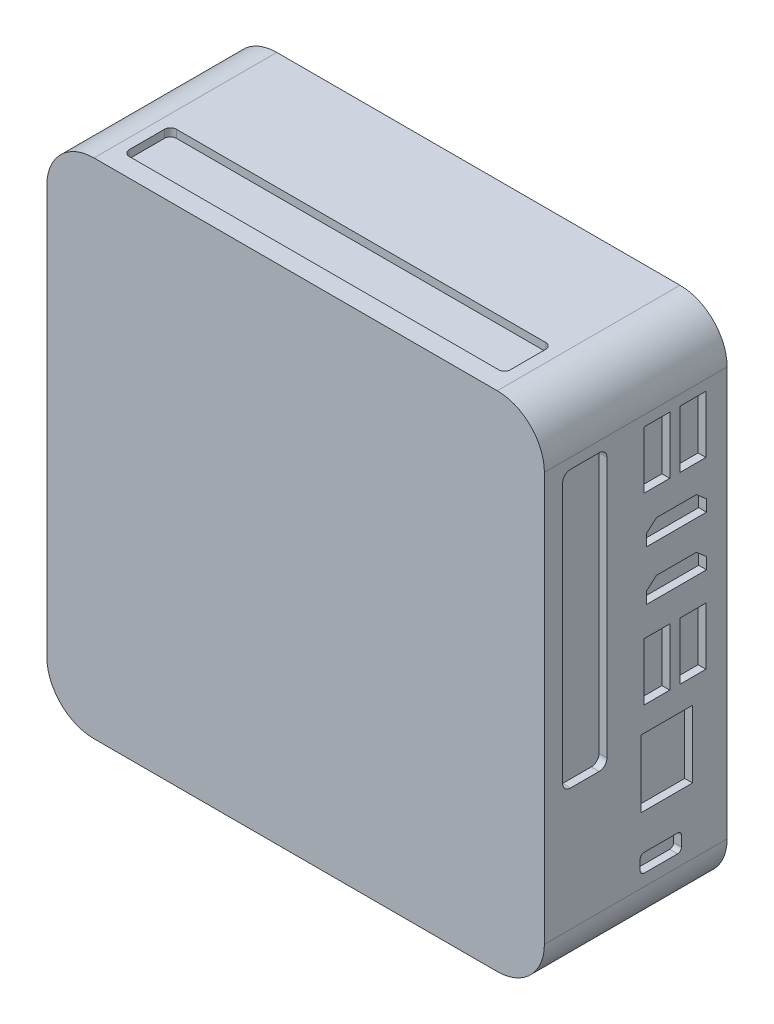
SolidWorks part; units mm, degrees
ref_plane "Płaszczyzna przednia" through (0, 0, 0) normal (0, 0, 1) x (1, 0, 0)
ref_plane "Płaszczyzna górna" through (0, 0, 0) normal (0, 1, 0) x (1, 0, 0)
ref_plane "Płaszczyzna prawa" through (0, 0, 0) normal (1, 0, 0) x (0, 0, -1)
sketch "Szkic1" plane through (0, 0, 0) normal (0, 0, 1) x (1, 0, 0)
  line L1 (-51.3, -64) -> (51.3, -64)
  line L2 (-63.3, -52) -> (-63.3, 52)
  line L3 (-51.3, 64) -> (51.3, 64)
  line L4 (63.3, -52) -> (63.3, 52)
  line L5 (-63.3, -64) -> (63.3, 64) construction
  line L6 (-63.3, 64) -> (63.3, -64) construction
  arc A0 (-51.3, -64) -> (-63.3, -52) centre (-51.3, -52) cw
  arc A1 (51.3, -64) -> (63.3, -52) centre (51.3, -52) ccw
  arc A2 (51.3, 64) -> (63.3, 52) centre (51.3, 52) cw
  arc A3 (-63.3, 52) -> (-51.3, 64) centre (-51.3, 52) cw
  point P0 (0, 0)
  dimension "D3" = 12
  dimension "D1" = 128
  dimension "D2" = 126.6
extrude "Dodanie-wyciągnięcie1" add sketch "Szkic1" along normal blind 46.5
sketch "Szkic2" plane through (0, 64, 0) normal (0, 1, 0) x (1, 0, 0)
  line L0 (-48.65, -31.2) -> (-48.65, -40.2)
  line L1 (-51.3, -46.5) -> (-51.3, 0) construction
  line L2 (-47.15, -29.7) -> (46.85, -29.7)
  line L3 (48.35, -31.2) -> (48.35, -40.2)
  line L4 (46.85, -41.7) -> (-47.15, -41.7)
  line L5 (51.3, -46.5) -> (-51.3, -46.5) construction
  arc A0 (48.35, -40.2) -> (46.85, -41.7) centre (46.85, -40.2) cw
  arc A1 (46.85, -29.7) -> (48.35, -31.2) centre (46.85, -31.2) cw
  arc A2 (-48.65, -40.2) -> (-47.15, -41.7) centre (-47.15, -40.2) ccw
  arc A3 (-48.65, -31.2) -> (-47.15, -29.7) centre (-47.15, -31.2) cw
  point P10 (48.35, -29.7)
  point P13 (-48.65, -41.7)
  point P16 (-48.65, -29.7)
  dimension "D4" = 1.5
  dimension "D1" = 12
  dimension "D2" = 2.65
  dimension "D3" = 97
  dimension "D5" = 4.8
extrude "Wytnij-wyciągnięcie1" cut sketch "Szkic2" against normal blind 2
sketch "Szkic3" plane through (-63.3, 0, 0) normal (-1, 0, 0) x (0, 0, 1)
  line L0 (29.5, -45.8) -> (38.5, -45.8)
  line L1 (46.5, -52) -> (0, -52) construction
  line L2 (28, -44.3) -> (28, 43.7)
  line L3 (29.5, 45.2) -> (38.5, 45.2)
  line L4 (40, 43.7) -> (40, -44.3)
  line L5 (46.5, 52) -> (46.5, -52) construction
  line L6 (15.3777, -23) -> (15.3777, -28.8) construction
  line L7 (17.0277, -23) -> (17.0277, -28.8)
  line L8 (13.7277, -23) -> (13.7277, -28.8)
  line L9 (15.3777, -3.9) -> (15.3777, -9.7) construction
  line L10 (17.0277, -3.9) -> (17.0277, -9.7)
  line L11 (13.7277, -3.9) -> (13.7277, -9.7)
  line L13 (13.3777, 32.6) -> (17.3777, 32.6)
  line L14 (12.3777, 31.6) -> (12.3777, 23.1)
  line L15 (13.3777, 22.1) -> (17.3777, 22.1)
  line L16 (18.3777, 31.6) -> (18.3777, 23.1)
  arc A0 (28, 43.7) -> (29.5, 45.2) centre (29.5, 43.7) cw
  arc A1 (38.5, 45.2) -> (40, 43.7) centre (38.5, 43.7) cw
  arc A2 (38.5, -45.8) -> (40, -44.3) centre (38.5, -44.3) ccw
  arc A3 (29.5, -45.8) -> (28, -44.3) centre (29.5, -44.3) cw
  arc A4 (17.0277, -23) -> (13.7277, -23) centre (15.3777, -23) ccw
  arc A5 (13.7277, -28.8) -> (17.0277, -28.8) centre (15.3777, -28.8) ccw
  arc A6 (17.0277, -3.9) -> (13.7277, -3.9) centre (15.3777, -3.9) ccw
  arc A7 (13.7277, -9.7) -> (17.0277, -9.7) centre (15.3777, -9.7) ccw
  circle A8 centre (15.3777, 10.1) radius 3.25
  arc A9 (13.3777, 32.6) -> (12.3777, 31.6) centre (13.3777, 31.6) ccw
  arc A10 (17.3777, 32.6) -> (18.3777, 31.6) centre (17.3777, 31.6) cw
  arc A11 (17.3777, 22.1) -> (18.3777, 23.1) centre (17.3777, 23.1) ccw
  arc A12 (12.3777, 23.1) -> (13.3777, 22.1) centre (13.3777, 23.1) ccw
  point P10 (28, 45.2)
  point P15 (40, -45.8)
  point P18 (28, -45.8)
  point P21 (15.3777, -25.9)
  point P26 (15.3777, -6.8)
  point P41 (12.3777, 32.6)
  point P46 (18.3777, 22.1)
  point P49 (12.3777, 22.1)
  dimension "D5" = 1.5
  dimension "D8" = 1.65
  dimension "D9" = 1.65
  dimension "D12" = 6.5
  dimension "D18" = 1
  dimension "D1" = 12
  dimension "D2" = 6.2
  dimension "D3" = 91
  dimension "D4" = 6.5
  dimension "D6" = 23.2
  dimension "D7" = 5.8
  dimension "D10" = 5.8
  dimension "D11" = 13.3
  dimension "D13" = 14
  dimension "D14" = 12
  dimension "D15" = 6
  dimension "D16" = 3
  dimension "D17" = 10.5
extrude "Wytnij-wyciągnięcie2" cut sketch "Szkic3" against normal blind 2 contours A3 L0 A2 L4 A1 L3 A0 L2 | L8 A5 L7 A4 | L11 A7 L10 A6 | A8 region at (-63.3, -0.3, 34) region at (-63.3, -25.9, 15.3777) region at (-63.3, -6.8, 15.3777) region at (-63.3, 10.1, 15.3777)
extrude "Dodanie-wyciągnięcie2" add sketch "Szkic3<3>" along normal blind 2 contours L14 A12 L15 A11 L16 A10 L13 A9 region at (-63.3, 27.35, 15.3777)
sketch "Szkic3<3>" plane through (-63.3, 0, 0) normal (-1, 0, 0) x (0, 0, 1) same geometry as "Szkic3"
mirror "Lustro1" about plane through (0, 0, 0) normal (0, 1, 0) of "Wytnij-wyciągnięcie1"
sketch "Szkic5" plane through (63.3, 0, 0) normal (1, 0, 0) x (0, 0, -1)
  line L0 (-39.86, 49.36) -> (-32.58, 49.36)
  line L1 (-46.5, 52) -> (0, 52) construction
  line L2 (-41.86, 47.36) -> (-41.86, -18.86)
  line L3 (-39.86, -20.86) -> (-32.58, -20.86)
  line L4 (-30.58, -18.86) -> (-30.58, 47.36)
  line L5 (-46.5, -52) -> (-46.5, 52) construction
  line L6 (-46.5, -52) -> (0, -52) construction
  line L7 (-21.12, -44.41) -> (-12.62, -44.41)
  line L8 (-22.12, -45.41) -> (-22.12, -48)
  line L9 (-21.12, -49) -> (-12.62, -49)
  line L10 (-11.62, -45.41) -> (-11.62, -48)
  line L11 (0, -52) -> (0, 52) construction
  line L12 (-12.01, -11.93) -> (-5.4, -11.93)
  line L13 (-21.92, -35.29) -> (-8.8, -35.29)
  line L14 (-21.92, -35.29) -> (-21.92, -18.16)
  line L15 (-21.92, -18.16) -> (-8.8, -18.16)
  line L16 (-8.8, -35.29) -> (-8.8, -18.16)
  line L17 (-12.01, -11.93) -> (-12.01, 2.67)
  line L18 (-12.01, 2.67) -> (-5.4, 2.67)
  line L19 (-5.4, 2.67) -> (-5.4, -11.93)
  line L20 (-21.21, -11.93) -> (-14.6, -11.93)
  line L21 (-14.6, 2.67) -> (-14.6, -11.93)
  line L22 (-21.21, 2.67) -> (-14.6, 2.67)
  line L23 (-21.21, -11.93) -> (-21.21, 2.67)
  line L24 (-20.57, 9.9) -> (-5.24, 9.9)
  line L25 (-5.24, 9.9) -> (-5.24, 12.83)
  line L27 (-7.82, 15.06) -> (-17.99, 15.06)
  line L28 (-17.99, 15.06) -> (-20.57, 12.83)
  line L29 (-20.57, 12.83) -> (-20.57, 9.9)
  line L30 (-7.82, 15.06) -> (-5.24, 12.83)
  line L31 (-7.82, 27.77) -> (-5.24, 25.54)
  line L32 (-5.24, 22.61) -> (-5.24, 25.54)
  line L33 (-20.57, 22.61) -> (-5.24, 22.61)
  line L34 (-20.57, 25.54) -> (-20.57, 22.61)
  line L35 (-17.99, 27.77) -> (-20.57, 25.54)
  line L36 (-7.82, 27.77) -> (-17.99, 27.77)
  line L37 (-21.21, 34.74) -> (-14.6, 34.74)
  line L38 (-14.6, 49.34) -> (-14.6, 34.74)
  line L39 (-21.21, 49.34) -> (-14.6, 49.34)
  line L40 (-21.21, 34.74) -> (-21.21, 49.34)
  line L41 (-5.4, 49.34) -> (-5.4, 34.74)
  line L42 (-12.01, 34.74) -> (-5.4, 34.74)
  line L43 (-12.01, 34.74) -> (-12.01, 49.34)
  line L44 (-12.01, 49.34) -> (-5.4, 49.34)
  arc A0 (-41.86, -18.86) -> (-39.86, -20.86) centre (-39.86, -18.86) ccw
  arc A1 (-32.58, -20.86) -> (-30.58, -18.86) centre (-32.58, -18.86) ccw
  arc A2 (-32.58, 49.36) -> (-30.58, 47.36) centre (-32.58, 47.36) cw
  arc A3 (-41.86, 47.36) -> (-39.86, 49.36) centre (-39.86, 47.36) cw
  arc A4 (-12.62, -44.41) -> (-11.62, -45.41) centre (-12.62, -45.41) cw
  arc A5 (-12.62, -49) -> (-11.62, -48) centre (-12.62, -48) ccw
  arc A6 (-22.12, -48) -> (-21.12, -49) centre (-21.12, -48) ccw
  arc A7 (-21.12, -44.41) -> (-22.12, -45.41) centre (-21.12, -45.41) ccw
  point P10 (-41.86, -20.86)
  point P15 (-30.58, 49.36)
  point P18 (-41.86, 49.36)
  point P29 (-11.62, -44.41)
  point P32 (-11.62, -49)
  dimension "D5" = 2
  dimension "D10" = 1
  dimension "D1" = 11.28
  dimension "D2" = 2.64
  dimension "D3" = 70.22
  dimension "D4" = 4.64
  dimension "D6" = 3
  dimension "D7" = 10.5
  dimension "D8" = 11.62
  dimension "D9" = 4.59
  dimension "D11" = 9.12
  dimension "D12" = 13.12
  dimension "D13" = 8.8
  dimension "D14" = 17.13
  dimension "D15" = 6.61
  dimension "D16" = 6.23
  dimension "D17" = 14.6
  dimension "D18" = 5.4
  dimension "D20" = 2.59
  dimension "D21" = 7.23
  dimension "D22" = 15.33
  dimension "D23" = 5.24
  dimension "D24" = 5.16
  dimension "D25" = 2.93
  dimension "D26" = 10.17
  dimension "D27" = 2.58
  dimension "D28" = 2.23
  dimension "D19" = 2
  dimension "D29" = 2
  dimension "D30" = 2
extrude "Wytnij-wyciągnięcie3" cut sketch "Szkic5" against normal blind 2
sketch "Sketch1" plane through (0, 0, 0) normal (0, 0, -1) x (-1, 0, 0)
  line L0 (43, 0) -> (0, 0) construction
  line L1 (0, 0) -> (-43, 0) construction
  circle A0 centre (-43, 0) radius 2
  circle A1 centre (43, 0) radius 2
  dimension "D1" = 4
  dimension "D2" = 86
extrude "Cut-Extrude1" cut sketch "Sketch1" against normal blind 5
